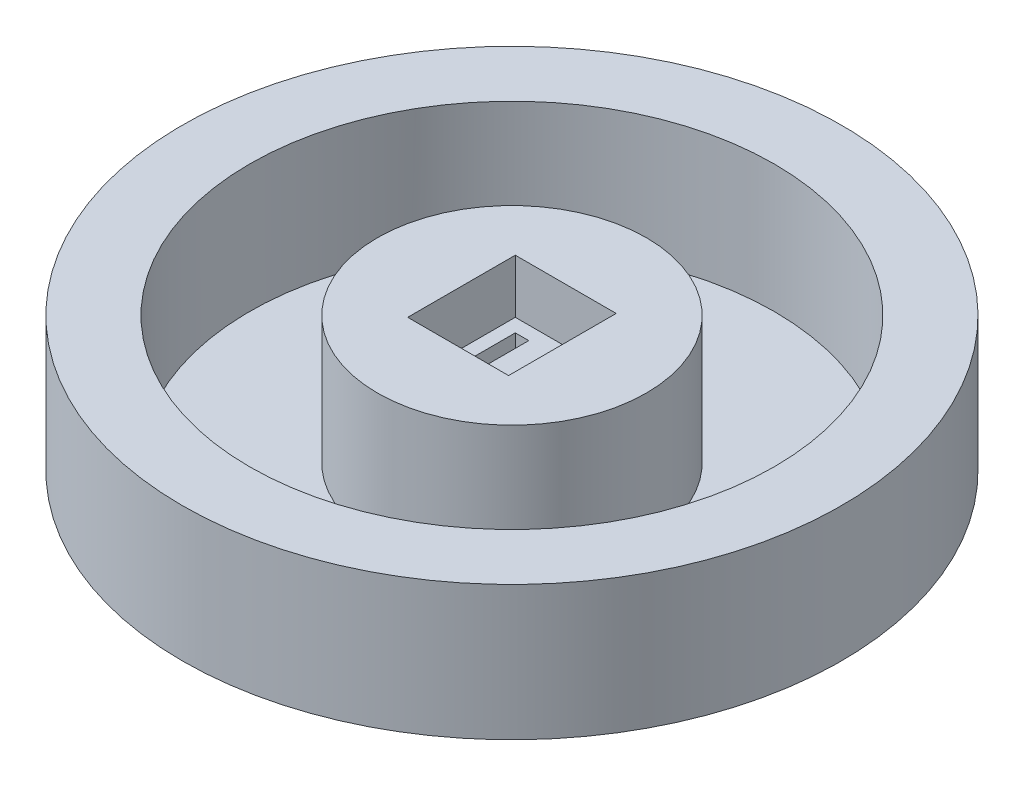
SolidWorks part; units mm, degrees
ref_plane "Front Plane" through (0, 0, 0) normal (0, 0, 1) x (1, 0, 0)
ref_plane "Top Plane" through (0, 0, 0) normal (0, 1, 0) x (1, 0, 0)
ref_plane "Right Plane" through (0, 0, 0) normal (1, 0, 0) x (0, 0, -1)
sketch "Sketch1" plane through (0, 0, 0) normal (0, 1, 0) x (1, 0, 0)
  circle A0 centre (0, 0) radius 49
  circle A1 centre (0, 0) radius 39
  dimension "D1" = 98
  dimension "D2" = 10
extrude "Boss-Extrude1" add sketch "Sketch1" along normal blind 20
sketch "Sketch2" plane through (0, 0, 0) normal (0, -1, 0) x (1, 0, 0)
  circle A0 centre (0, 0) radius 39 construction
  circle A1 centre (0, 0) radius 39
extrude "Boss-Extrude2" add sketch "Sketch2" against normal blind 1
sketch "Sketch3" plane through (0, 1, 0) normal (0, 1, 0) x (1, 0, 0)
  circle A0 centre (0, 0) radius 20
  dimension "D1" = 40
extrude "Boss-Extrude3" add sketch "Sketch3" along normal up to surface (19 mm away) up to face at (0, 20, 49)
sketch "Sketch4" plane through (0, 20, 0) normal (0, 1, 0) x (1, 0, 0)
  line L1 (-7.5, -8) -> (7.5, -8)
  line L2 (-7.5, -8) -> (-7.5, 8)
  line L3 (-7.5, 8) -> (7.5, 8)
  line L4 (7.5, -8) -> (7.5, 8)
  line L5 (-7.5, -8) -> (7.5, 8) construction
  line L6 (-7.5, 8) -> (7.5, -8) construction
  point P0 (0, 0)
  dimension "D1" = 15
  dimension "D2" = 16
extrude "Cut-Extrude1" cut sketch "Sketch4" against normal blind 8
sketch "Sketch5" plane through (0, 0, 0) normal (0, -1, 0) x (1, 0, 0)
  line L1 (-9, -9) -> (9, -9)
  line L2 (-9, -9) -> (-9, 9)
  line L3 (-9, 9) -> (9, 9)
  line L4 (9, -9) -> (9, 9)
  line L5 (-9, -9) -> (9, 9) construction
  line L6 (-9, 9) -> (9, -9) construction
  point P0 (0, 0)
  dimension "D1" = 18
  dimension "D2" = 18
extrude "Cut-Extrude2" cut sketch "Sketch5" against normal offset from surface (10 mm away) 2 up to face at (0, 12, 0)
sketch "Sketch6" plane through (0, 12, 0) normal (0, 1, 0) x (1, 0, 0)
  line L0 (0, 0) -> (-7.5, 0) construction
  line L1 (-7.5, 8) -> (-7.5, -8) construction
  line L2 (0, 0) -> (7.5, 0) construction
  line L3 (7.5, -8) -> (7.5, 8) construction
  line L4 (7.5, -8) -> (7.5, 8) construction
  line L5 (-5.5, 6) -> (-3.5, 6)
  line L6 (-5.5, 6) -> (-5.5, -6)
  line L7 (-5.5, -6) -> (-3.5, -6)
  line L8 (-3.5, 6) -> (-3.5, -6)
  line L9 (-5.5, 6) -> (-3.5, -6) construction
  line L10 (-5.5, -6) -> (-3.5, 6) construction
  line L11 (5.5, 6) -> (3.5, 6)
  line L12 (5.5, 6) -> (5.5, -6)
  line L13 (5.5, -6) -> (3.5, -6)
  line L14 (3.5, 6) -> (3.5, -6)
  line L15 (5.5, 6) -> (3.5, -6) construction
  line L16 (5.5, -6) -> (3.5, 6) construction
  point P5 (-4.5, 0)
  point P13 (4.5, 0)
  dimension "D1" = 2
  dimension "D2" = 2
  dimension "D3" = 12
  dimension "D4" = 2
extrude "Cut-Extrude3" cut sketch "Sketch6" against normal through all
